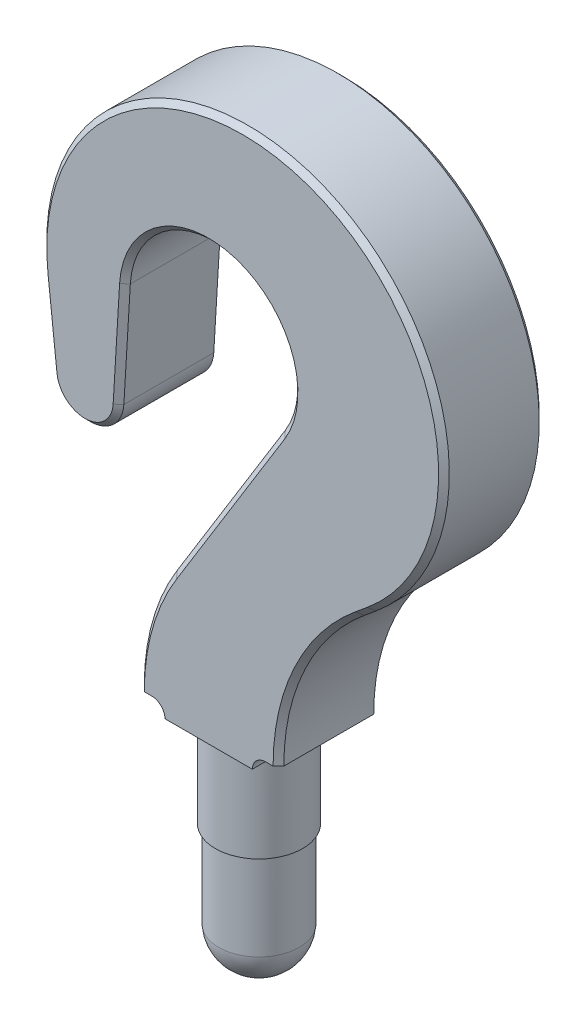
SolidWorks part; units mm, degrees
ref_plane "Front Plane" through (0, 0, 0) normal (0, 0, 1) x (1, 0, 0)
ref_plane "Top Plane" through (0, 0, 0) normal (0, 1, 0) x (1, 0, 0)
ref_plane "Right Plane" through (0, 0, 0) normal (1, 0, 0) x (0, 0, -1)
sketch "Sketch1" plane through (0, 0, 0) normal (0, 0, 1) x (1, 0, 0)
  line L0 (0, 0) -> (-5.07, 0) construction
  line L1 (-5.07, 0) -> (-5.07, -52) construction
  line L2 (-5.07, -52) -> (38.33, -52) construction
  line L3 (38.33, -52) -> (38.33, -50.05) construction
  line L4 (38.33, -50.05) -> (17.53, -50.05) construction
  line L5 (5.33, -50.05) -> (3.4294, -50.05)
  line L6 (5.5712, -6.5586) -> (-10.5627, -32.7352)
  line L7 (-11.57, -52) -> (1.43, -52)
  line L8 (19.0894, -23.1429) -> (17.3317, -24.5928)
  line L9 (-5.07, -15) -> (-23.5, -15) construction
  line L10 (-29.8199, -3.2821) -> (-28.47, -15.547)
  line L11 (-17.5476, 0.7475) -> (-18.5089, -15.299)
  line L12 (-13.5694, -50.05) -> (-15.47, -50.05)
  arc A0 (19.0894, -23.1429) -> (-29.8199, -3.2821) centre (0, 0) ccw
  arc A1 (5.5712, -6.5586) -> (-17.5476, 0.7475) centre (-5.07, 0) ccw
  arc A2 (17.3317, -24.5928) -> (5.33, -50.05) centre (38.33, -50.05) ccw
  arc A3 (-10.5627, -32.7352) -> (-15.47, -50.05) centre (17.53, -50.05) ccw
  arc A4 (-11.57, -52) -> (-13.5694, -50.05) centre (-13.5694, -52.05) ccw
  arc A6 (1.43, -52) -> (3.4294, -50.05) centre (3.4294, -52.05) cw
  arc A7 (-28.47, -15.547) -> (-18.5089, -15.299) centre (-23.5, -15) ccw
  point P17 (-5.07, -52)
  dimension "D1" = 60
  dimension "D3" = 25
  dimension "D7" = 66
  dimension "D9" = 66
  dimension "D11" = 4
  dimension "D14" = 10
  dimension "D2" = 5.07
  dimension "D4" = 52
  dimension "D5" = 43.4
  dimension "D6" = 1.95
  dimension "D8" = 20.8
  dimension "D10" = 13
  dimension "D12" = 18.43
  dimension "D13" = 15
extrude "Boss-Extrude1" add sketch "Sketch1" along normal blind 15
chamfer "Chamfer1" distance 0.8 angle 45 18 edges at (-14.2195, -41.0516, 0) (-2.4958, -19.6469, 0) (-1.3033, 11.919, 0) (-18.0283, -7.2757, 0) (8.4808, -35.9778, 0) (-23.3755, -19.9985, 0) (18.2105, -23.8679, 0) (-29.145, -9.4146, 0) (11.2871, 27.7957, 0) (-14.2195, -41.0516, 15) (-2.4958, -19.6469, 15) (-1.3033, 11.919, 15) (-18.0283, -7.2757, 15) (8.4808, -35.9778, 15) (-23.3755, -19.9985, 15) (18.2105, -23.8679, 15) (-29.145, -9.4146, 15) (11.2871, 27.7957, 15)
sketch "Sketch2" plane through (0, -52, 0) normal (0, -1, 0) x (1, 0, 0)
  line L0 (1.43, 15) -> (1.43, 0) construction
  line L1 (-11.57, 0) -> (1.43, 0) construction
  line L2 (-11.57, 15) -> (-11.57, 0) construction
  line L3 (-11.57, 15) -> (1.43, 15) construction
  line L4 (1.43, 15) -> (1.43, 0)
  line L5 (-11.57, 0) -> (1.43, 0)
  line L6 (-11.57, 15) -> (-11.57, 0)
  line L7 (-11.57, 15) -> (1.43, 15)
  line L8 (1.43, 15) -> (-11.57, 0) construction
  line L9 (-11.57, 15) -> (1.43, 0) construction
  circle A0 centre (-5.07, 7.5) radius 6.5
  point P3 (-5.07, 7.5)
  dimension "D1" = 13
extrude "Boss-Extrude2" add sketch "Sketch2" along normal blind 14 contours A0 region at (-5.07, -52, 7.5)
sketch "Sketch3" plane through (0, -66, 0) normal (0, -1, 0) x (1, 0, 0)
  circle A0 centre (-5.07, 7.5) radius 6.5 construction
  circle A1 centre (-5.07, 7.5) radius 6.5
  circle A2 centre (-5.07, 7.5) radius 6
  dimension "D1" = 12
extrude "Boss-Extrude3" add sketch "Sketch3" along normal blind 13 contours A2 region at (-5.07, -66, 7.5)
cosmetic thread "Cosmetic Thread1" parameters "D2"=10.072
dome "Dome1" faces to dome 1 distance 5.61 reverse direction no elliptical dome no face at (-5.07, -79, 1.5) parameters "D1"=5.61
